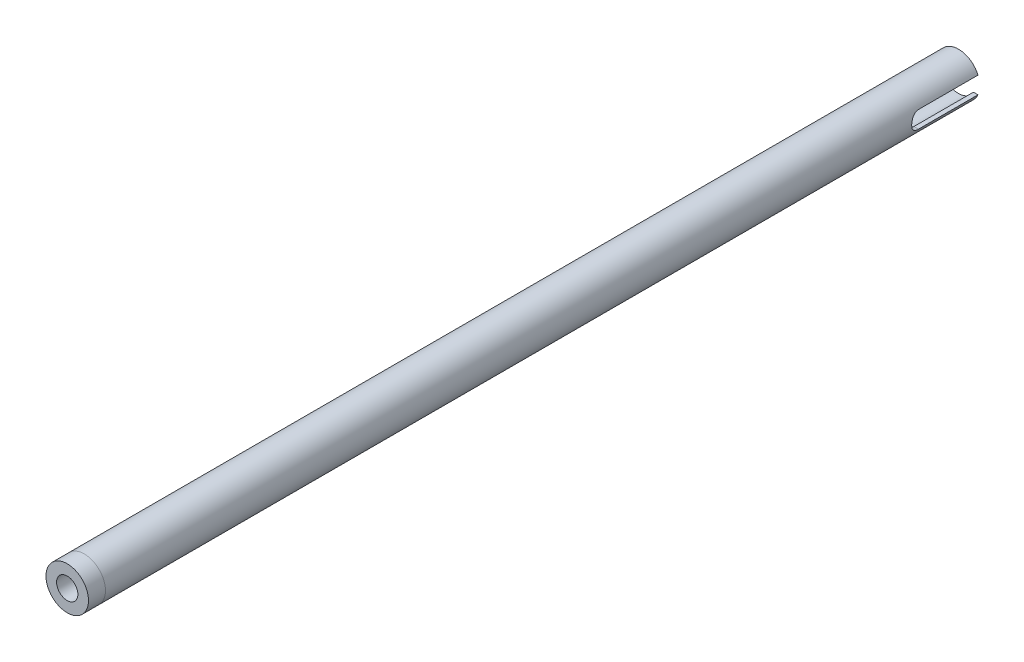
SolidWorks part; units mm, degrees
ref_plane "Front Plane" through (0, 0, 0) normal (0, 0, 1) x (1, 0, 0)
ref_plane "Top Plane" through (0, 0, 0) normal (0, 1, 0) x (1, 0, 0)
ref_plane "Right Plane" through (0, 0, 0) normal (1, 0, 0) x (0, 0, -1)
sketch "Axis" plane through (0, 0, 0) normal (0, 1, 0) x (1, 0, 0)
  line L0 (0, 0) -> (0, 332.6562) construction
  line L1 (0, 0) -> (0, -28.575) construction
  line L2 (0, 332.6562) -> (-7.9375, 332.6562) construction
  line L3 (0, 361.4076) -> (-10.3188, 324.0308) construction
  dimension "D1" = 28.575
  dimension "D2" = 7.9375
sketch "Sketch1" plane through (0, 0, 0) normal (0, 0, 1) x (1, 0, 0)
  line L0 (-7.9375, 0) -> (7.9375, 0) construction
  line L1 (-7.2748, 3.175) -> (7.2748, 3.175)
  line L2 (-7.2748, -3.175) -> (7.2748, -3.175)
  circle A0 centre (0, 0) radius 7.9375
  circle A1 centre (0, 0) radius 6.4135
  circle A2 centre (0, 0) radius 3.9688
  dimension "D1" = 15.875
  dimension "D3" = 7.9375
  dimension "D2" = 1.524
  dimension "D4" = 6.35
extrude "Threaded insert 1-1" add sketch "Sketch1" against normal blind 6.35 contours A2 L1 A1 | A1 L1 A0 | A2 L0 A1 L1 | A1 L0 A0 L1 | L0 A1 L2 A0 | L0 A2 L2 A1 | A2 L2 A1 | A1 L2 A0 | L0 A1 L2 A2 | L0 A0 L2 A1 | A0 L0 A1 L1 | A1 L0 A2 L1 region at (4.7887, 1.6543, 0) region at (4.7887, -1.6543, 0) region at (6.9234, 1.6163, 0) region at (6.9234, -1.6163, 0) region at (-4.7887, -1.6543, 0) region at (-4.7887, 1.6543, 0) region at (0, 4.6159, 0) region at (0, -4.6159, 0) region at (0, 6.5666, 0) region at (6.4237, -3.3281, 0) region at (-6.9234, -1.6163, 0) region at (-6.9234, 1.6163, 0)
extrude "Threaded insert 1-2" add sketch "Sketch1<3>" against normal blind 9.525 from surface contours A2 L1 A1 | A2 L0 A1 L1 | L0 A2 L2 A1 | A2 L2 A1 | L0 A1 L2 A2 | A1 L0 A2 L1 region at (4.7887, 1.6543, 0) region at (4.7887, -1.6543, 0) region at (-4.7887, -1.6543, 0) region at (-4.7887, 1.6543, 0) region at (0, 4.6159, 0) region at (0, -4.6159, 0) starting at face at (7.9375, 0, -6.35)
sketch "Sketch1<3>" plane through (0, 0, 0) normal (0, 0, 1) x (1, 0, 0) same geometry as "Sketch1"
extrude "A-arm tube" add sketch "Sketch1<4>" against normal up to vertex (332.6562 mm away) from surface separate body contours A1 L1 A0 | A1 L0 A0 L1 | L0 A1 L2 A0 | A1 L2 A0 | L0 A0 L2 A1 | A0 L0 A1 L1 region at (6.9234, 1.6163, 0) region at (6.9234, -1.6163, 0) region at (0, 6.5666, 0) region at (6.4237, -3.3281, 0) region at (-6.9234, -1.6163, 0) region at (-6.9234, 1.6163, 0) up to point (0, 0, -332.6562) starting at face at (6.4135, 0, -6.35)
sketch "Sketch1<4>" plane through (0, 0, 0) normal (0, 0, 1) x (1, 0, 0) same geometry as "Sketch1"
extrude "Apex slot" cut sketch "Sketch1<5>" along normal blind 25.4 from surface contours A0 L0 A1 L1 | L0 A0 L2 A1 | A1 L0 A0 L1 | L0 A1 L2 A0 region at (6.9234, 1.6163, 0) region at (6.9234, -1.6163, 0) region at (-6.9234, -1.6163, 0) region at (-6.9234, 1.6163, 0) starting at face at (6.4135, 0, -332.6562)
sketch "Sketch1<5>" plane through (0, 0, 0) normal (0, 0, 1) x (1, 0, 0) same geometry as "Sketch1"
fillet "Fillet1" radius 3.175 4 edges at (-6.4237, 3.175, -307.2562) (-6.4237, -3.175, -307.2562) (6.4237, -3.175, -307.2562) (6.4237, 3.175, -307.2562)
equation "\"tube diameter\"= 5 / 8"
equation "\"tube thickness\"= .06"
equation "\"apex thickness\"= .25"
equation "\"tube slot\"= 1"
equation "\"D1@Sketch1\"=\"tube diameter\""
equation "\"D2@Sketch1\"=\"tube thickness\""
equation "\"threaded insert hole\"= .3125"
equation "\"D3@Sketch1\"=\"threaded insert hole\""
equation "\"D4@Sketch1\"=\"apex thickness\""
equation "\"D1@Apex slot\" = \"tube slot\""
equation "\"D1@Fillet1\"=\"apex thickness\"/2"
equation "\"D2@Axis\"=\"tube diameter\"/2"
